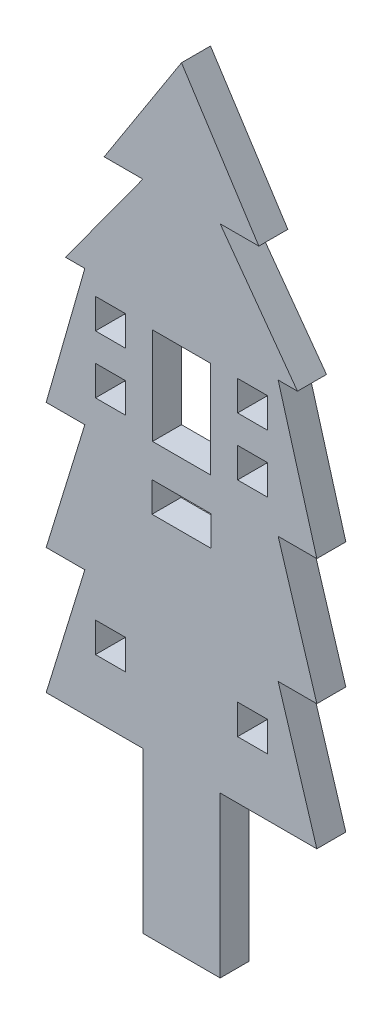
SolidWorks part; units mm, degrees
ref_plane "Ebene vorne (XY)" through (0, 0, 0) normal (0, 0, 1) x (1, 0, 0)
ref_plane "Ebene oben  (XZ)" through (0, 0, 0) normal (0, 1, 0) x (1, 0, 0)
ref_plane "Ebene rechts  (YZ)" through (0, 0, 0) normal (1, 0, 0) x (0, 0, -1)
ref_axis "x-Achse" through (-15.4, 0, 0) along (1, 0, 0)
ref_axis "y-Achse" through (0, 34.4272, 0) along (0, -1, 0)
ref_axis "z-Achse" through (0, 0, -0.15) along (0, 0, 1)
sketch "Profile_Laser_profile_3mm" plane through (0, 0, 0) normal (0, 0, 1) x (1, 0, 0)
  line L0 (0, 30.4272) -> (8, 18)
  line L1 (8, 18) -> (4, 18)
  line L2 (4, 18) -> (12, 7)
  line L3 (12, 7) -> (10, 7)
  line L4 (10, 7) -> (14, -7)
  line L5 (14, -7) -> (10, -7)
  line L6 (10, -7) -> (14, -20)
  line L7 (14, -20) -> (10, -20)
  line L8 (10, -20) -> (14, -33)
  line L9 (14, -33) -> (4, -33)
  line L10 (4, -33) -> (4, -49.5728)
  line L11 (4, -49.5728) -> (-4, -49.5728)
  line L12 (-4, -49.5728) -> (-4, -33)
  line L13 (-4, -33) -> (-14, -33)
  line L14 (-14, -33) -> (-10, -20)
  line L15 (-10, -20) -> (-14, -20)
  line L16 (-14, -20) -> (-10, -7)
  line L17 (-10, -7) -> (-14, -7)
  line L18 (-14, -7) -> (-10, 7)
  line L19 (-10, 7) -> (-12, 7)
  line L20 (-12, 7) -> (-4, 18)
  line L21 (-4, 18) -> (-8, 18)
  line L22 (-8, 18) -> (0, 30.4272)
  line L23 (-8.9, 1.95) -> (-5.8, 1.95)
  line L24 (-5.8, 1.95) -> (-5.8, 5.05)
  line L25 (-5.8, 5.05) -> (-8.9, 5.05)
  line L26 (-8.9, 5.05) -> (-8.9, 1.95)
  line L27 (-8.9, -4.05) -> (-5.8, -4.05)
  line L28 (-5.8, -4.05) -> (-5.8, -0.95)
  line L29 (-5.8, -0.95) -> (-8.9, -0.95)
  line L30 (-8.9, -0.95) -> (-8.9, -4.05)
  line L31 (-8.9, -27.05) -> (-5.8, -27.05)
  line L32 (-5.8, -27.05) -> (-5.8, -23.95)
  line L33 (-5.8, -23.95) -> (-8.9, -23.95)
  line L34 (-8.9, -23.95) -> (-8.9, -27.05)
  line L35 (5.8, 1.95) -> (8.9, 1.95)
  line L36 (8.9, 1.95) -> (8.9, 5.05)
  line L37 (8.9, 5.05) -> (5.8, 5.05)
  line L38 (5.8, 5.05) -> (5.8, 1.95)
  line L39 (5.8, -4.05) -> (8.9, -4.05)
  line L40 (8.9, -4.05) -> (8.9, -0.95)
  line L41 (8.9, -0.95) -> (5.8, -0.95)
  line L42 (5.8, -0.95) -> (5.8, -4.05)
  line L43 (5.8, -27.05) -> (8.9, -27.05)
  line L44 (8.9, -27.05) -> (8.9, -23.95)
  line L45 (8.9, -23.95) -> (5.8, -23.95)
  line L46 (5.8, -23.95) -> (5.8, -27.05)
  line L47 (-3.05, -11.55) -> (3.05, -11.55)
  line L48 (3.05, -11.55) -> (3.05, -8.45)
  line L49 (3.05, -8.45) -> (-3.05, -8.45)
  line L50 (-3.05, -8.45) -> (-3.05, -11.55)
  line L51 (-3, -5) -> (3, -5)
  line L52 (3, -5) -> (3, 5)
  line L53 (3, 5) -> (-3, 5)
  line L54 (-3, 5) -> (-3, -5)
extrude "Laser_profile_3mm" add sketch "Profile_Laser_profile_3mm" along normal blind 3
